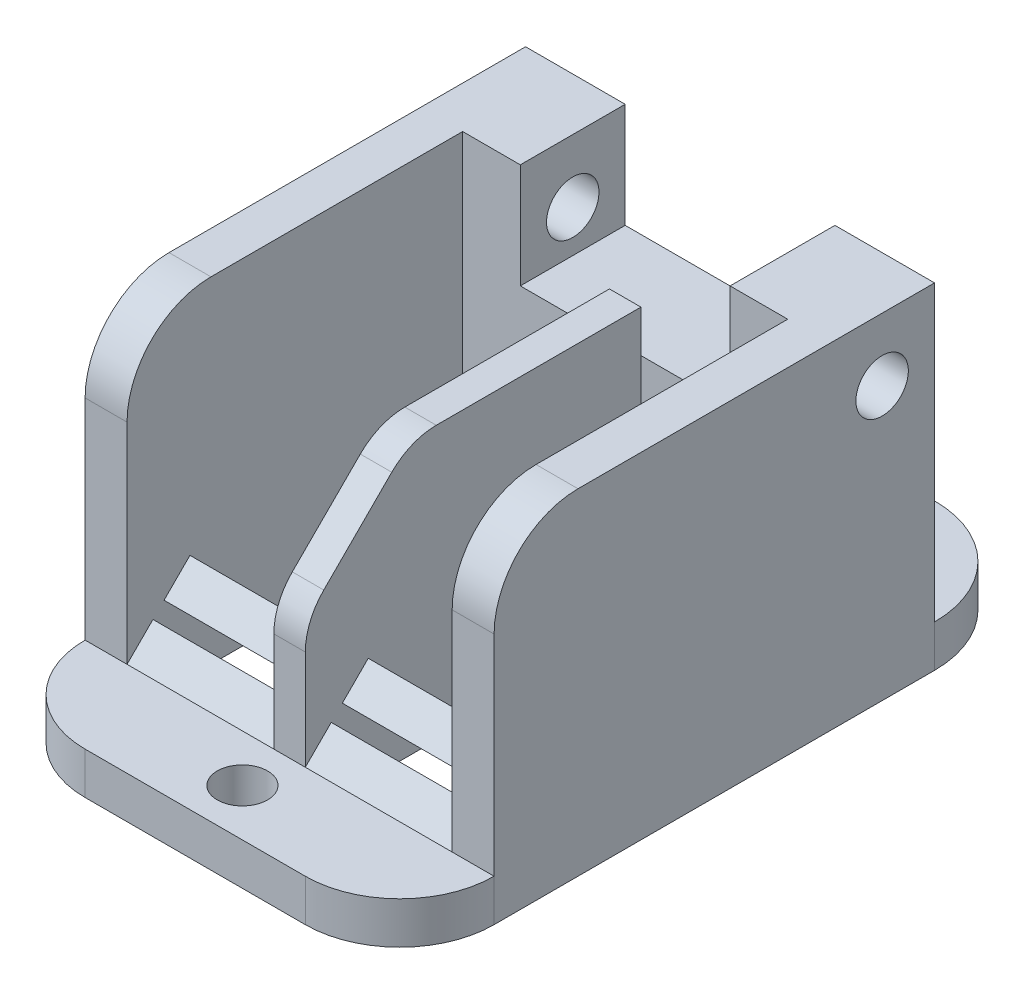
SolidWorks part; units mm, degrees
ref_plane "Front Plane" through (0, 0, 0) normal (0, 0, 1) x (1, 0, 0)
ref_plane "Top Plane" through (0, 0, 0) normal (0, 1, 0) x (1, 0, 0)
ref_plane "Right Plane" through (0, 0, 0) normal (1, 0, 0) x (0, 0, -1)
sketch "Usable Area" plane through (0, 0, 0) normal (0, 1, 0) x (1, 0, 0)
  line L0 (-6.17, -37.332) -> (-38.9, -37.332)
  line L1 (-38.9, -37.332) -> (-38.9, -6.17)
  line L2 (0, -34.15) -> (-6.07, -34.15)
  line L3 (-6.17, -34.25) -> (-6.17, -37.332)
  line L4 (-34.15, 0) -> (-34.15, -6.17)
  line L5 (-38.9, -6.17) -> (-34.15, -6.17)
  line L6 (0, -20.5) -> (0, -34.15)
  line L7 (-20.5, 0) -> (-34.15, 0)
  arc A0 (-20.5, 0) -> (0, -20.5) centre (0, 0) ccw
sketch "Sketch8" plane through (0, 0, 0) normal (0, 1, 0) x (1, 0, 0)
  line L1 (-37.4, -12.17) -> (-37.4, -33.17)
  line L2 (-37.4, -33.17) -> (-35.4, -33.17)
  line L3 (-35.4, -33.17) -> (-35.4, -17.17)
  line L4 (-35.4, -17.17) -> (-19.9, -17.17)
  line L5 (-19.9, -17.17) -> (-19.9, -33.17)
  line L6 (-19.9, -33.17) -> (-17.9, -33.17)
  line L7 (-17.9, -33.17) -> (-17.9, -12.17)
  line L8 (-38.9, -37.332) -> (-38.9, -6.17) construction
  line L14 (-37.4, -12.17) -> (-17.9, -12.17)
  line L15 (-38.9, -6.17) -> (-34.15, -6.17) construction
  dimension "D1" = 1.5
  dimension "D2" = 5
  dimension "D3" = 6
  dimension "D5" = 15.5
  dimension "D6" = 2
  dimension "D7" = 16
  dimension "D8" = 2
extrude "Boss-Extrude7" add sketch "Sketch8" along normal blind 16
sketch "Sketch9" plane through (0, 0, 0) normal (0, 1, 0) x (1, 0, 0)
  line L0 (-35.4, -17.17) -> (-19.9, -17.17) construction
  line L1 (-28.4, -17.17) -> (-26.9, -17.17)
  line L2 (-28.4, -17.17) -> (-28.4, -33.17)
  line L3 (-28.4, -33.17) -> (-26.9, -33.17)
  line L4 (-26.9, -17.17) -> (-26.9, -33.17)
  line L5 (-35.4, -33.17) -> (-35.4, -17.17) construction
  line L6 (-37.4, -33.17) -> (-35.4, -33.17) construction
  dimension "D1" = 7
  dimension "D2" = 1.5
extrude "Boss-Extrude8" add sketch "Sketch9" along normal blind 13
sketch "Sketch10" plane through (0, 0, 0) normal (0, 1, 0) x (1, 0, 0)
  line L0 (-37.4, -12.17) -> (-37.4, -33.17) construction
  line L1 (-37.4, -30.17) -> (-17.9, -30.17)
  line L2 (-37.4, -30.17) -> (-37.4, -33.17)
  line L3 (-32.9, -37.67) -> (-22.4, -37.67)
  line L4 (-17.9, -30.17) -> (-17.9, -33.17)
  line L5 (-17.9, -33.17) -> (-17.9, -12.17) construction
  arc A0 (-22.4, -37.67) -> (-17.9, -33.17) centre (-22.4, -33.17) ccw
  arc A1 (-37.4, -33.17) -> (-32.9, -37.67) centre (-32.9, -33.17) ccw
  point P8 (0, 0)
  point P9 (0, 0)
  point P15 (0, 0)
  dimension "D2" = 4.5
  dimension "D3" = 4.5
  dimension "D1" = 3
extrude "Boss-Extrude9" add sketch "Sketch10" along normal blind 2
fillet "Fillet1" radius 4 2 edges at (-18.9, 16, 33.17) (-36.4, 16, 33.17)
sketch "Sketch11" plane through (0, 16, 0) normal (0, 1, 0) x (1, 0, 0)
  line L0 (-17.9, -12.17) -> (-37.4, -12.17) construction
  line L1 (-32.65, -12.17) -> (-22.65, -12.17)
  line L2 (-32.65, -12.17) -> (-32.65, -17.17)
  line L3 (-32.65, -17.17) -> (-22.65, -17.17)
  line L4 (-22.65, -12.17) -> (-22.65, -17.17)
  line L5 (-35.4, -17.17) -> (-19.9, -17.17) construction
  point P8 (-27.65, -12.17)
  dimension "D1" = 10
extrude "Cut-Extrude1" cut sketch "Sketch11" against normal blind 5
chamfer "Chamfer2" distance 5 angle 45 1 edges at (-27.65, 13, 33.17)
fillet "Fillet2" radius 3 2 edges at (-27.65, 8, 33.17) (-27.65, 13, 28.17)
ref_plane "Plane1" through (-27.65, 0, 0) normal (-1, 0, 0) x (0, 0, 1)
sketch "Sketch12" plane through (-27.65, 0, 0) normal (-1, 0, 0) x (0, 0, 1)
  line L0 (12.17, 11) -> (12.17, 16) construction
  line L1 (12.17, 16) -> (17.17, 16) construction
  circle A0 centre (14.67, 13) radius 1.25
  dimension "D3" = 2.5
  dimension "D1" = 2.5
  dimension "D2" = 3
extrude "Cut-Extrude2" cut sketch "Sketch12" against normal mid plane 25
sketch "Sketch15" plane through (0, 2, 0) normal (0, 1, 0) x (1, 0, 0)
  line L4 (-27.65, -35.42) -> (-27.65, -37.67) construction
  line L5 (-32.9, -37.67) -> (-22.4, -37.67) construction
  point P0 (0, 0)
  point P1 (0, 0)
  dimension "D1" = 2.25
hole_wizard "M2 Clearance Hole1" positions "3DSketch1" profile "Sketch16" hole size "M2" standard "ANSI Metric" end condition through all
sketch3d "3DSketch1"
  point P0 (-27.65, 2, 35.42)
sketch "Sketch16" plane through (-27.65, 2, 35.42) normal (1, 0, 0) x (0, 0, 1)
  line L0 (0, 0) -> (0, 2)
  line L1 (0, 2) -> (1.2, 2)
  line L2 (1.2, 2) -> (1.2, 0)
  line L5 (1.2, 0) -> (0, 0)
  line L11 (0, -6.35) -> (0, 107.95) construction
  dimension "Thru Hole Dia." = 2.4
  dimension "Thru Hole Depth" = 2
sketch "Sketch17" plane through (0, 0, 0) normal (0, 1, 0) x (1, 0, 0)
  line L0 (-37.4, -12.17) -> (-37.4, -29.17) construction
  line L1 (-32.4, -7.17) -> (-22.9, -7.17)
  line L2 (-37.4, -12.17) -> (-37.4, -14.17)
  line L3 (-37.4, -14.17) -> (-17.9, -14.17)
  line L4 (-17.9, -12.17) -> (-17.9, -14.17)
  line L5 (-17.9, -29.17) -> (-17.9, -12.17) construction
  arc A0 (-22.9, -7.17) -> (-17.9, -12.17) centre (-22.9, -12.17) cw
  arc A1 (-32.4, -7.17) -> (-37.4, -12.17) centre (-32.4, -12.17) ccw
  point P5 (0, 0)
  point P14 (0, 0)
  dimension "D1" = 5
  dimension "D2" = 5
  dimension "D3" = 2
extrude "Boss-Extrude10" add sketch "Sketch17" along normal blind 2
sketch "Sketch18" plane through (0, 2, 0) normal (0, 1, 0) x (1, 0, 0)
  line L0 (-27.65, -7.17) -> (-27.65, -12.17) construction
  line L1 (-22.9, -7.17) -> (-32.4, -7.17) construction
  line L2 (-17.9, -12.17) -> (-37.4, -12.17) construction
  line L3 (-31.65, -9.67) -> (-23.65, -9.67) construction
  point P9 (-27.65, -9.67)
  dimension "D1" = 8
hole_wizard "M2 Clearance Hole2" positions "3DSketch2" profile "Sketch19" hole size "M2" standard "ANSI Metric" end condition through all
sketch3d "3DSketch2"
  point P0 (-31.65, 2, 9.67)
  point P3 (-23.65, 2, 9.67)
sketch "Sketch19" plane through (-31.65, 2, 9.67) normal (1, 0, 0) x (0, 0, 1)
  line L0 (0, 0) -> (0, 2)
  line L1 (0, 2) -> (1.2, 2)
  line L2 (1.2, 2) -> (1.2, 0)
  line L5 (1.2, 0) -> (0, 0)
  line L11 (0, -6.35) -> (0, 107.95) construction
  dimension "Thru Hole Dia." = 2.4
  dimension "Thru Hole Depth" = 2
sketch "Sketch20" plane through (0, 0, 0) normal (0, 1, 0) x (1, 0, 0)
  line L1 (-35.4, -33.17) -> (-19.9, -33.17)
  line L2 (-35.4, -33.17) -> (-35.4, -25.17)
  line L3 (-35.4, -25.17) -> (-19.9, -25.17)
  line L4 (-19.9, -33.17) -> (-19.9, -25.17)
  point P6 (0, 0)
  point P7 (0, 0)
  dimension "D1" = 8
extrude "Boss-Extrude11" add sketch "Sketch20" along normal blind 5.5
chamfer "Chamfer3" distance 5.5 angle 45 2 edges at (-31.9, 5.5, 25.17) (-23.4, 5.5, 25.17)
chamfer "Chamfer4" distance 3.5 angle 45 2 edges at (-23.4, 5.5, 33.17) (-31.9, 5.5, 33.17)
sketch "Sketch21" plane through (0, 17.585, 17.585) normal (0, 0.7071, 0.7071) x (1, 0, 0)
  line L0 (-35.4, -22.0405) -> (-35.4, -17.7979) construction
  line L1 (-35.4, -20.2942) -> (-28.4, -20.2942)
  line L2 (-35.4, -20.2942) -> (-35.4, -19.5442)
  line L3 (-35.4, -19.5442) -> (-28.4, -19.5442)
  line L4 (-28.4, -20.2942) -> (-28.4, -19.5442)
  line L5 (-28.4, -17.7979) -> (-28.4, -22.0405) construction
  point P8 (-35.4, -19.9192)
  dimension "D1" = 0.75
extrude "Cut-Extrude3" cut sketch "Sketch21" against normal through all
pattern_linear "LPattern1" count 2 spacing 8.5 along (1, 0, 0) of "Cut-Extrude3"
